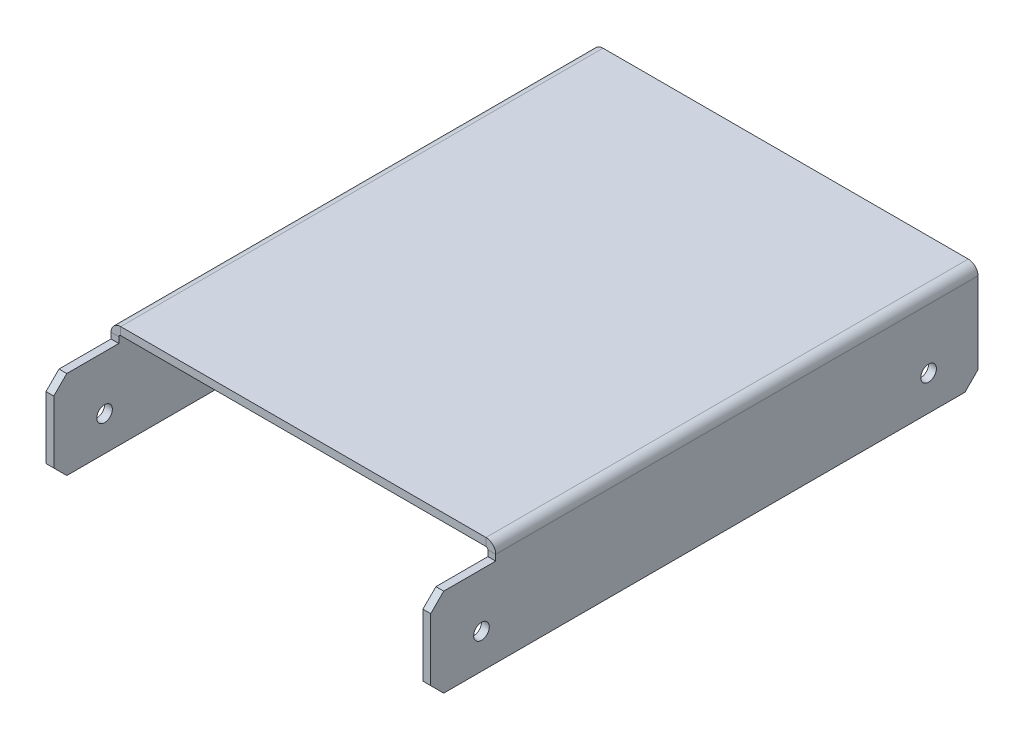
SolidWorks part; units mm, degrees
note: The reader was unsure of these and kept them because the rebuilt part matched: flange length of "Edge-Flange1".
ref_plane "정면" through (0, 0, 0) normal (0, 0, 1) x (1, 0, 0)
ref_plane "윗면" through (0, 0, 0) normal (0, 1, 0) x (1, 0, 0)
ref_plane "우측면" through (0, 0, 0) normal (1, 0, 0) x (0, 0, -1)
sketch "Sketch18" plane through (0, 0, 0) normal (0, 1, 0) x (1, 0, 0)
  line L1 (-148, -166.3369) -> (0, -166.3369)
  line L2 (-148, -166.3369) -> (-148, 39.1965)
  line L3 (-148, 39.1965) -> (0, 39.1965)
  line L4 (0, -166.3369) -> (0, 39.1965)
  dimension "D1" = 205.5334
  dimension "D2" = 148
base flange "Base-Flange1" sketch "Sketch18" thickness 3 reverse thickness direction no parameters "D1"=0.7366
edge flange "Edge-Flange1" sketch "Sketch25" flange profiles "Sketch25", "Sketch26" flange angle 90 flange length 40 flange position material inside bend radius 0.7366 thickness 3 parameters "D6"=10, "D8"=1
sketch "Sketch25" plane through (0, -3, 0) normal (1, 0, 0) x (0, 0, 1)
  line L2 (-39.1965, 0) -> (-39.1965, 37)
  line L3 (-39.1965, 37) -> (166.3369, 37)
  line L4 (166.3369, 37) -> (166.3369, 0)
  line L7 (166.3369, 0) -> (-39.1965, 0) construction
  line L8 (166.3369, 0) -> (-39.1965, 0)
sketch "Sketch26" plane through (-148, -3, 0) normal (-1, 0, 0) x (0, 0, -1)
  line L0 (39.1965, 0) -> (-166.3369, 0) construction
  line L1 (39.1965, 0) -> (-166.3369, 0)
  line L2 (-166.3369, 0) -> (-166.3369, 37)
  line L3 (-166.3369, 37) -> (39.1965, 37)
  line L4 (39.1965, 37) -> (39.1965, 0)
bend "EdgeBend1" bend radius 0.7366 bend angle 90 parameters "D5"=1
bend "EdgeBend2" bend radius 0.7366 bend angle 90 parameters "D5"=2
sketch "Sketch27" plane through (-148, 0, 0) normal (-1, 0, 0) x (0, 0, 1)
  line L0 (-39.1965, -40) -> (166.3369, -40) construction
  line L1 (-39.1965, -3.7366) -> (-39.1965, -40) construction
  line L2 (166.3369, -40) -> (166.3369, -3.7366) construction
  circle A0 centre (-25.1965, -26.64) radius 3
  circle A1 centre (146.8069, -26.64) radius 3
  dimension "D1" = 6
  dimension "D2" = 13.36
  dimension "D4" = 19.53
  dimension "D5" = 13.36
  dimension "D3" = 14
extrude "Cut-Extrude1" cut sketch "Sketch27" against normal through all
sketch "Sketch28" plane through (0, 0, 166.3369) normal (0, 0, 1) x (1, 0, 0)
  line L1 (-159, -6) -> (1, -6)
  line L2 (-159, -6) -> (-159, 2)
  line L3 (-159, 2) -> (1, 2)
  line L4 (1, -6) -> (1, 2)
  dimension "D1" = 8
  dimension "D2" = 160
extrude "Cut-Extrude2" cut sketch "Sketch28" against normal blind 25
sketch "Sketch32" plane through (0, 0, -39.1965) normal (0, 0, -1) x (-1, 0, 0)
  line L0 (0, -3.7366) -> (0, -40) construction
  line L1 (0, -40) -> (3, -40) construction
  line L2 (3, -40) -> (3, -3.7366) construction
  line L3 (145, -3.7366) -> (145, -40) construction
  line L4 (145, -40) -> (148, -40) construction
  line L5 (148, -40) -> (148, -3.7366) construction
  line L6 (3.7366, -3) -> (144.2634, -3) construction
  line L7 (144.2634, 0) -> (3.7366, 0) construction
  line L8 (0, -3.7366) -> (0, -40)
  line L9 (0, -40) -> (3, -40)
  line L10 (3, -40) -> (3, -3.7366)
  line L11 (145, -3.7366) -> (145, -40)
  line L12 (145, -40) -> (148, -40)
  line L13 (148, -40) -> (148, -3.7366)
  line L14 (3.7366, -3) -> (144.2634, -3)
  line L15 (144.2634, 0) -> (3.7366, 0)
  arc A0 (3.7366, -3) -> (3, -3.7366) centre (3.7366, -3.7366) ccw construction
  arc A1 (3.7366, 0) -> (0, -3.7366) centre (3.7366, -3.7366) ccw construction
  arc A2 (145, -3.7366) -> (144.2634, -3) centre (144.2634, -3.7366) ccw construction
  arc A3 (148, -3.7366) -> (144.2634, 0) centre (144.2634, -3.7366) ccw construction
  arc A4 (3.7366, -3) -> (3, -3.7366) centre (3.7366, -3.7366) ccw
  arc A5 (3.7366, 0) -> (0, -3.7366) centre (3.7366, -3.7366) ccw
  arc A6 (145, -3.7366) -> (144.2634, -3) centre (144.2634, -3.7366) ccw
  arc A7 (148, -3.7366) -> (144.2634, 0) centre (144.2634, -3.7366) ccw
extrude "Boss-Extrude1" add sketch "Sketch32" along normal blind 5
chamfer "Chamfer2" distance 5 angle 45 6 edges at (-1.5, -6, 166.3369) (-146.5, -6, 166.3369) (-146.5, -40, -44.1965) (-1.5, -40, -44.1965) (-1.5, -40, 166.3369) (-146.5, -40, 166.3369)
sketch "굽힘 선1" [suppressed] plane through (0, 0, 0) normal (0, 1, 0) x (1, 0, 0)
sketch "경계 상자1" [suppressed] plane through (0, 0, 0) normal (0, 1, 0) x (1, 0, 0)
sheet metal parameters "Sheet-Metal97" thickness 3 parameters "D1"=0.7366
flat pattern "Flat-Pattern97" [suppressed]
sketch "굽힘 선2" plane through (0, 0, 0) normal (0, 1, 0) x (1, 0, 0)
sketch3d "경계 상자2" [suppressed]
  line L0 (150, -166.3369, 0) -> (150, 39.1965, 0) construction
  line L1 (0, -166.3369, 0) -> (0, 39.1965, 0) construction
  line L2 (150, -166.3369, 0) -> (0, -166.3369, 0) construction
  line L3 (150, 39.1965, 0) -> (0, 39.1965, 0) construction
sheet metal parameters "Sheet-Metal98" thickness 3 parameters "D1"=0.7366
flat pattern "Flat-Pattern97"
sketch "굽힘 선2" plane through (0, 0, 0) normal (0, 1, 0) x (1, 0, 0)
  line L0 (-148.02, 39.1965) -> (-148.02, -166.3369) construction
  line L1 (-1.98, -166.3369) -> (-1.98, 39.1965) construction
  line L2 (-148.02, 39.1965) -> (-148.02, -166.3369) construction
  line L3 (-1.98, -166.3369) -> (-1.98, 39.1965) construction
sketch3d "경계 상자2" [suppressed]
  line L0 (-176.04, -166.3369, 0) -> (-176.04, 39.1965, 0) construction
  line L1 (26.04, -166.3369, 0) -> (26.04, 39.1965, 0) construction
  line L2 (-176.04, -166.3369, 0) -> (26.04, -166.3369, 0) construction
  line L3 (-176.04, 39.1965, 0) -> (26.04, 39.1965, 0) construction
bend of the flat pattern "Flatten-<EdgeBend1>1"
bend of the flat pattern "Flatten-<EdgeBend2>1"
sheet metal parameters "Sheet-Metal99" thickness 3 parameters "D1"=0.7366
flat pattern "Flat-Pattern97"
sketch "굽힘 선2" plane through (0, 0, 0) normal (0, 1, 0) x (1, 0, 0)
  line L0 (-137.02, 39.1965) -> (-137.02, -166.3369) construction
  line L1 (-1.98, -166.3369) -> (-1.98, 39.1965) construction
  line L2 (-137.02, 39.1965) -> (-137.02, -166.3369) construction
  line L3 (-1.98, -166.3369) -> (-1.98, 39.1965) construction
sketch3d "경계 상자2" [suppressed]
  line L0 (36.04, 39.1965, 0) -> (-175.04, 39.1965, 0) construction
  line L1 (36.04, -166.3369, 0) -> (-175.04, -166.3369, 0) construction
  line L2 (36.04, 39.1965, 0) -> (36.04, -166.3369, 0) construction
  line L3 (-175.04, 39.1965, 0) -> (-175.04, -166.3369, 0) construction
bend of the flat pattern "Flatten-<EdgeBend1>1"
bend of the flat pattern "Flatten-<EdgeBend2>1"
sheet metal parameters "Sheet-Metal100" thickness 3 parameters "D1"=0.7366
flat pattern "Flat-Pattern97"
sketch "굽힘 선2" plane through (0, 0, 0) normal (0, 1, 0) x (1, 0, 0)
  line L0 (-146.02, 39.1965) -> (-146.02, -141.3369) construction
  line L1 (-1.98, -141.3369) -> (-1.98, 39.1965) construction
  line L2 (-146.02, 39.1965) -> (-146.02, -141.3369) construction
  line L3 (-1.98, -141.3369) -> (-1.98, 39.1965) construction
sketch3d "경계 상자2" [suppressed]
  line L0 (36.04, 39.1965, 0) -> (-184.04, 39.1965, 0) construction
  line L1 (36.04, -166.3369, 0) -> (-184.04, -166.3369, 0) construction
  line L2 (36.04, 39.1965, 0) -> (36.04, -166.3369, 0) construction
  line L3 (-184.04, 39.1965, 0) -> (-184.04, -166.3369, 0) construction
bend of the flat pattern "Flatten-<EdgeBend1>1"
bend of the flat pattern "Flatten-<EdgeBend2>1"
sheet metal parameters "Sheet-Metal102" thickness 3 parameters "D1"=0.7366
flat pattern "Flat-Pattern97"
sketch "굽힘 선2" plane through (0, 0, 0) normal (0, 1, 0) x (1, 0, 0)
  line L0 (-146.02, 44.1965) -> (-146.02, -141.3369) construction
  line L1 (-1.98, -141.3369) -> (-1.98, 44.1965) construction
  line L2 (-146.02, 44.1965) -> (-146.02, -141.3369) construction
  line L3 (-1.98, -141.3369) -> (-1.98, 44.1965) construction
sketch3d "경계 상자2" [suppressed]
  line L0 (36.04, 44.1965, 0) -> (-184.04, 44.1965, 0) construction
  line L1 (36.04, -166.3369, 0) -> (-184.04, -166.3369, 0) construction
  line L2 (36.04, 44.1965, 0) -> (36.04, -166.3369, 0) construction
  line L3 (-184.04, 44.1965, 0) -> (-184.04, -166.3369, 0) construction
bend of the flat pattern "Flatten-<EdgeBend1>1"
bend of the flat pattern "Flatten-<EdgeBend2>1"
